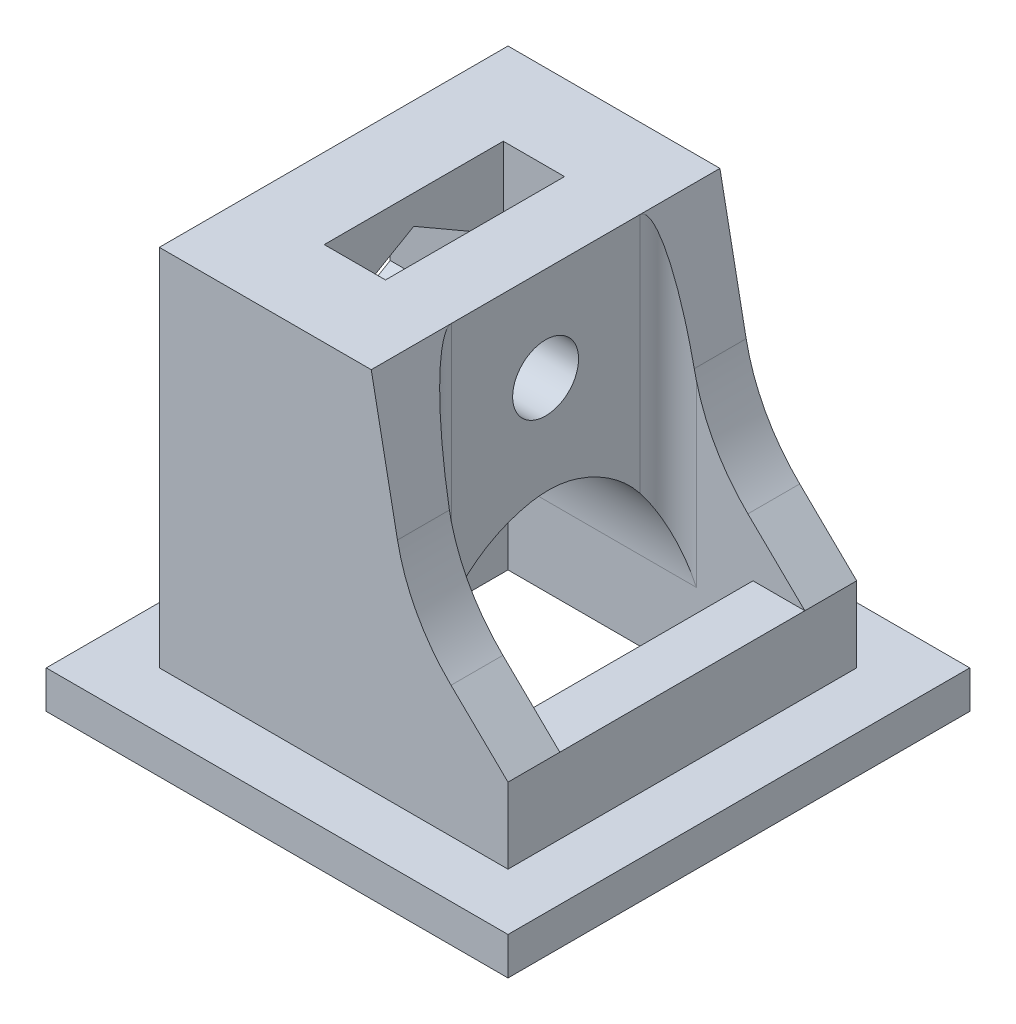
SolidWorks part; units mm, degrees
material "PBT Общее назначение"
ref_plane "Спереди" through (0, 0, 0) normal (0, 0, 1) x (1, 0, 0)
ref_plane "Сверху" through (0, 0, 0) normal (0, 1, 0) x (1, 0, 0)
ref_plane "Справа" through (0, 0, 0) normal (1, 0, 0) x (0, 0, -1)
sketch "Эскиз1" plane through (0, 0, 0) normal (0, 1, 0) x (1, 0, 0)
  line L0 (0, 0) -> (18.5, 0)
  line L1 (0, 0) -> (0, 18.5)
  line L2 (18.5, 0) -> (18.5, 18.5)
  line L3 (0, 18.5) -> (18.5, 18.5)
  line L4 (2.75, 15.75) -> (2.75, 2.75)
  line L5 (2.75, 15.75) -> (15.75, 15.75)
  line L6 (2.75, 2.75) -> (15.75, 2.75)
  line L7 (15.75, 15.75) -> (15.75, 2.75)
  line L8 (9.25, 18.5) -> (9.25, 0) construction
  line L9 (18.5, 9.25) -> (0, 9.25) construction
  line L10 (2.75, 9.25) -> (15.75, 9.25) construction
  line L11 (9.25, 15.75) -> (9.25, 2.75) construction
  dimension "D1" = 18.5
  dimension "D3" = 13
extrude "Бобышка-Вытянуть1" add sketch "Эскиз1" along normal blind 4
sketch "Эскиз2" plane through (0, 0, 0) normal (0, 0, 1) x (1, 0, 0)
  line L0 (0, 4) -> (18.5, 4)
  line L1 (18.5, 4) -> (0, 22)
  line L2 (0, 4) -> (0, 22)
  dimension "D1" = 18
extrude "Бобышка-Вытянуть2" add sketch "Эскиз2" against normal up to surface (18.5 mm away) up to face at (9.25, 2, -18.5)
sketch "Эскиз3" plane through (0, 4, 0) normal (0, -1, 0) x (1, 0, 0)
  line L4 (2.75, -2.75) -> (2.75, -15.75)
  line L5 (2.75, -15.75) -> (15.75, -15.75)
  line L6 (15.75, -15.75) -> (15.75, -2.75)
  line L7 (15.75, -2.75) -> (2.75, -2.75)
  line L8 (2.75, -2.75) -> (2.75, -15.75)
  line L9 (2.75, -15.75) -> (15.75, -15.75)
  line L10 (15.75, -15.75) -> (15.75, -2.75)
  line L11 (15.75, -2.75) -> (2.75, -2.75)
  dimension "D1" = 0
extrude "Вырез-Вытянуть1" cut sketch "Эскиз3" against normal through all
sketch "Эскиз4" plane through (15.75, 0, 0) normal (-1, 0, 0) x (0, 0, 1)
  line L0 (0, 4) -> (-18.5, 4) construction
  line L1 (-2.75, 4) -> (-15.75, 4)
  line L2 (-2.75, 6.6757) -> (-2.75, 0) construction
  line L3 (-2.75, 6.6757) -> (-2.75, 4)
  line L4 (-15.75, 6.6757) -> (-15.75, 0) construction
  line L5 (-15.75, 6.6757) -> (-15.75, 4)
  line L6 (-2.75, 6.6757) -> (-15.75, 6.6757) construction
  line L7 (-2.75, 6.6757) -> (-15.75, 6.6757)
extrude "Вырез-Вытянуть2" cut sketch "Эскиз4" against normal through all
sketch "Эскиз6" plane through (0, 0, -18.5) normal (0, 0, -1) x (-1, 0, 0)
  line L1 (-2.75, 19.3243) -> (-2.75, 0) construction
  line L2 (-2.75, 19.3243) -> (0, 19.3243)
  line L3 (0, 22) -> (0, 0) construction
  line L4 (0, 22) -> (0, 19.3243)
  line L5 (0, 22) -> (-18.5, 4) construction
  line L6 (0, 22) -> (-2.75, 19.3243)
  line L7 (-2.75, 19.3243) -> (-2.75, 0) construction
extrude "Вырез-Вытянуть3" cut sketch "Эскиз6" against normal through all
sketch "Эскиз7" plane through (0, 0, 0) normal (0, -1, 0) x (1, 0, 0)
  line L0 (0, -9.25) -> (18.5, -9.25) construction
  line L1 (0, -18.5) -> (0, 0) construction
  line L2 (18.5, 0) -> (18.5, -18.5) construction
  line L3 (9.25, -18.5) -> (9.25, 0) construction
  line L4 (18.5, -18.5) -> (0, -18.5) construction
  line L5 (0, 0) -> (18.5, 0) construction
sketch "Эскиз9" plane through (0, 0, 0) normal (0, -1, 0) x (1, 0, 0)
  line L0 (15.75, -2.75) -> (15.75, -15.75) construction
  line L1 (15.75, -15.75) -> (2.75, -15.75) construction
  line L2 (2.75, -15.75) -> (2.75, -2.75) construction
  line L3 (2.75, -2.75) -> (15.75, -2.75) construction
  line L4 (0, 0) -> (0, -18.5)
  line L5 (0, -18.5) -> (18.5, -18.5)
  line L6 (18.5, -18.5) -> (18.5, 0)
  line L7 (18.5, 0) -> (0, 0)
  line L8 (0, 0) -> (0, -18.5)
  line L9 (0, -18.5) -> (18.5, -18.5)
  line L10 (18.5, -18.5) -> (18.5, 0)
  line L11 (18.5, 0) -> (0, 0)
  line L12 (15.75, -2.75) -> (15.75, -15.75)
  line L13 (15.75, -15.75) -> (2.75, -15.75)
  line L14 (2.75, -15.75) -> (2.75, -2.75)
  line L15 (2.75, -2.75) -> (15.75, -2.75)
  dimension "D1" = 0
extrude "Бобышка-Вытянуть4" add sketch "Эскиз9" along normal blind 2
sketch "Эскиз10" plane through (0, -2, 0) normal (0, -1, 0) x (1, 0, 0)
  line L0 (21.5, -21.5) -> (-3, -21.5)
  line L1 (21.5, -21.5) -> (21.5, 3)
  line L2 (-3, -21.5) -> (-3, 3)
  line L3 (21.5, 3) -> (-3, 3)
  line L4 (2.75, -15.75) -> (15.75, -15.75) construction
  line L5 (15.75, -15.75) -> (15.75, -2.75) construction
  line L6 (2.75, -2.75) -> (2.75, -15.75) construction
  line L7 (15.75, -2.75) -> (2.75, -2.75) construction
  line L8 (2.75, -15.75) -> (15.75, -15.75)
  line L9 (15.75, -15.75) -> (15.75, -2.75)
  line L10 (2.75, -2.75) -> (2.75, -15.75)
  line L11 (15.75, -2.75) -> (2.75, -2.75)
  line L12 (9.25, -21.5) -> (9.25, 3) construction
  line L13 (-3, -9.25) -> (21.5, -9.25) construction
  line L14 (18.5, -18.5) -> (18.5, 0) construction
  line L15 (0, -18.5) -> (18.5, -18.5) construction
  point P12 (18.5, -9.25)
  point P13 (9.25, -18.5)
  dimension "D1" = 24.5
extrude "Бобышка-Вытянуть5" add sketch "Эскиз10" against normal blind 2
sketch "Эскиз12" plane through (0, 0, -15.75) normal (0, 0, 1) x (1, 0, 0)
  line L0 (2.75, 19.3243) -> (2.75, -2) construction
  line L1 (18.5, 4) -> (2.75, 19.3243) construction
  line L2 (2.75, 19.3243) -> (2.75, 6)
  line L3 (4.25, 17.8649) -> (2.75, 19.3243)
  line L4 (2.75, -2) -> (15.75, -2) construction
  line L5 (4.25, 9.1225) -> (4.25, 17.8649)
  arc A0 (4.25, 9.1225) -> (2.75, 6) centre (6.75, 6) ccw
  dimension "D2" = 4
  dimension "D1" = 1.5
  dimension "D3" = 8
extrude "Бобышка-Вытянуть6" add sketch "Эскиз12" along normal up to surface (13 mm away) up to face at (11.1, 4.6649, -2.75)
sketch "Эскиз13" plane through (0, 0, 0) normal (-1, 0, 0) x (0, 0, 1)
  line L0 (-9.25, 19.3243) -> (-9.25, 8.0835) construction
  line L1 (0, 19.3243) -> (-18.5, 19.3243) construction
  circle A0 centre (-9.25, 14.3243) radius 1.75
  dimension "D1" = 3.5
  dimension "D2" = 5
extrude "Вырез-Вытянуть4" cut sketch "Эскиз13" against normal through all
sketch "Эскиз15" plane through (0, 0, -15.75) normal (0, 0, 1) x (1, 0, 0)
  line L0 (4.25, 9.1225) -> (4.25, 17.8649) construction
  line L1 (4.25, 9.1225) -> (4.25, 17.8649)
  line L2 (18.5, 4) -> (4.25, 17.8649) construction
  line L3 (7.25, 14.9459) -> (4.25, 17.8649)
  line L4 (4.25, 9.1225) -> (7.25, 11.9459)
  line L5 (7.25, 11.9459) -> (7.25, 14.9459)
  dimension "D2" = 3
  dimension "D1" = 3
extrude "Бобышка-Вытянуть7" add sketch "Эскиз15" along normal blind 1.75
ref_plane "Плоскость1" through (0, 0, -9.25) normal (0, 0, -1) x (1, 0, 0)
mirror "Зеркальное отражение1" about plane through (0, 0, -9.25) normal (0, 0, -1) of "Бобышка-Вытянуть7"
sketch "Эскиз16" plane through (0, 0, 0) normal (0, 0, 1) x (1, 0, 0)
  line L1 (7.25, 11.9459) -> (7.25, 14.9459) construction
  line L2 (18.5, 4) -> (2.75, 19.3243) construction
  line L3 (7.25, 14.9459) -> (2.75, 19.3243)
  line L4 (7.25, 14.9459) -> (7.25, 19.3243)
  line L6 (2.75, 19.3243) -> (7.25, 19.3243)
extrude "Бобышка-Вытянуть8" add sketch "Эскиз16" against normal up to surface (18.5 mm away) up to face at (7.95, 8.5297, -18.5)
sketch "Эскиз17" plane through (0, 19.3243, 0) normal (0, 1, 0) x (1, 0, 0)
  line L4 (7.25, 14) -> (4.25, 14)
  line L5 (7.25, 4.5) -> (7.25, 14)
  line L6 (4.25, 4.5) -> (7.25, 4.5)
  line L7 (4.25, 14) -> (4.25, 4.5)
  line L8 (7.25, 14) -> (4.25, 14)
  line L9 (7.25, 4.5) -> (7.25, 14)
  line L10 (4.25, 4.5) -> (7.25, 4.5)
  line L11 (4.25, 14) -> (4.25, 4.5)
  dimension "D1" = 0
extrude "Вырез-Вытянуть6" cut sketch "Эскиз17" against normal through all
fillet "Скругление1" radius 15 1 edges at (7.25, 14.9459, -1.375)
fillet "Скругление2" radius 15 1 edges at (7.25, 14.9459, -17.125)
sketch "Эскиз18" plane through (7.25, 0, 0) normal (1, 0, 0) x (0, 0, -1)
  line L4 (4.5, 19.3243) -> (2.75, 19.3243)
  line L5 (2.75, 19.3243) -> (2.75, 11.9459)
  line L6 (2.75, 11.9459) -> (4.5, 11.9459)
  line L7 (4.5, 11.9459) -> (4.5, 19.3243)
  line L8 (4.5, 19.3243) -> (2.75, 19.3243)
  line L9 (2.75, 19.3243) -> (2.75, 11.9459)
  line L10 (2.75, 11.9459) -> (4.5, 11.9459)
  line L11 (4.5, 11.9459) -> (4.5, 19.3243)
  line L12 (15.75, 11.9459) -> (15.75, 19.3243)
  line L13 (15.75, 19.3243) -> (14, 19.3243)
  line L14 (14, 19.3243) -> (14, 11.9459)
  line L15 (14, 11.9459) -> (15.75, 11.9459)
  line L16 (15.75, 11.9459) -> (15.75, 19.3243)
  line L17 (15.75, 19.3243) -> (14, 19.3243)
  line L18 (14, 19.3243) -> (14, 11.9459)
  line L19 (14, 11.9459) -> (15.75, 11.9459)
  dimension "D1" = 0
  dimension "D2" = 0
extrude "Бобышка-Вытянуть9" add sketch "Эскиз18" along normal up to surface (3.2258 mm away) up to face at (9.0866, 14.816, -1.375)
sketch "Эскиз19" plane through (0, 0, 0) normal (-1, 0, 0) x (0, 0, 1)
  circle A0 centre (-9.25, 14.3243) radius 1.75 construction
  circle A1 centre (-9.25, 14.3243) radius 1.75 construction
  circle A2 centre (-9.25, 14.3243) radius 5
  dimension "D1" = 10
sketch "Эскиз14" plane through (0, 0, 0) normal (-1, 0, 0) x (0, 0, 1)
  line L0 (-9.25, 14.3243) -> (-9.25, 17.7884) construction
  line L1 (-9.25, 10.8602) -> (-6.25, 12.5923)
  line L2 (-6.25, 12.5923) -> (-6.25, 16.0564)
  line L3 (-6.25, 16.0564) -> (-9.25, 17.7884)
  line L4 (-9.25, 17.7884) -> (-12.25, 16.0564)
  line L5 (-12.25, 16.0564) -> (-12.25, 12.5923)
  line L6 (-12.25, 12.5923) -> (-9.25, 10.8602)
  circle A0 centre (-9.25, 14.3243) radius 3 construction
  dimension "D1" = 6
extrude "Вырез-Вытянуть5" cut sketch "Эскиз14" along normal through all and the other way up to surface (4.25 mm away) other way up to face at (4.25, 14.3243, -7.5)
sketch "Эскиз21" plane through (0, 0, -4.5) normal (0, 0, -1) x (-1, 0, 0)
  line L0 (-4.25, 9.1225) -> (-7.25, 11.9459) construction
  line L1 (-10.4758, 11.9459) -> (-7.25, 11.9459) construction
  line L2 (-4.25, 9.1225) -> (-7.25, 11.9459)
  line L3 (-10.4758, 11.9459) -> (-7.25, 11.9459)
  line L4 (-4.25, 9.1225) -> (-13.5183, 9.1225)
  arc A0 (-11.6421, 10.6726) -> (-10.4758, 11.9459) centre (-22.1024, 21.4235) ccw construction
  arc A1 (-13.5183, 9.1225) -> (-10.4758, 11.9459) centre (-22.1024, 21.4235) ccw
extrude "Бобышка-Вытянуть11" add sketch "Эскиз21" against normal up to surface (1.75 mm away) up to face at (9.8604, 5.9823, -2.75)
sketch "Эскиз22" plane through (0, 0, -14) normal (0, 0, 1) x (1, 0, 0)
  line L0 (10.4758, 11.9459) -> (7.25, 11.9459) construction
  line L1 (4.25, 9.1225) -> (7.25, 11.9459) construction
  line L2 (10.4758, 11.9459) -> (7.25, 11.9459)
  line L3 (4.25, 9.1225) -> (7.25, 11.9459)
  line L4 (4.25, 9.1225) -> (13.5183, 9.1225)
  arc A0 (10.4758, 11.9459) -> (11.6421, 10.6726) centre (22.1024, 21.4235) ccw construction
  arc A1 (10.4758, 11.9459) -> (13.5183, 9.1225) centre (22.1024, 21.4235) ccw
extrude "Бобышка-Вытянуть12" add sketch "Эскиз22" against normal up to surface (1.75 mm away) up to face at (9.8604, 5.9823, -15.75)
sketch "Эскиз23" plane through (0, 0, -15.75) normal (0, 0, -1) x (-1, 0, 0)
  line L2 (-13.2352, 9.1225) -> (-11.6421, 10.6726)
  line L3 (-13.5183, 9.1225) -> (-13.2352, 9.1225)
  line L4 (-13.2352, 9.1225) -> (-11.6421, 10.6726)
  line L5 (-13.5183, 9.1225) -> (-13.2352, 9.1225)
  arc A1 (-13.5183, 9.1225) -> (-11.6421, 10.6726) centre (-22.1024, 21.4235) ccw
  arc A2 (-13.5183, 9.1225) -> (-11.6421, 10.6726) centre (-22.1024, 21.4235) ccw
  dimension "D1" = 0
extrude "Вырез-Вытянуть7" cut sketch "Эскиз23" against normal through all
sketch "Эскиз20" plane through (0, 19.3243, 0) normal (0, 1, 0) x (1, 0, 0)
  line L0 (7.25, 0) -> (7.25, 18.5)
  line L1 (7.25, 0) -> (13.2352, 0)
  line L2 (7.25, 18.5) -> (13.2352, 18.5)
  line L5 (13.2352, 2.75) -> (13.2352, 4.5) construction
  line L6 (13.2352, 0) -> (13.2352, 18.5)
extrude "Бобышка-Вытянуть15" add sketch "Эскиз20" against normal up to surface (4.3784 mm away) up to face at (14.4591, 7.9317, -2.4167)
sketch "Эскиз25" plane through (0, 0, -4.5) normal (0, 0, -1) x (-1, 0, 0)
  line L0 (-13.2352, 9.1225) -> (-4.25, 9.1225) construction
  line L1 (-13.2352, 9.1225) -> (-7.25, 9.1225)
  line L2 (-7.25, 14.9459) -> (-13.2352, 9.1225) construction
  line L3 (-7.25, 14.9459) -> (-13.2352, 9.1225)
  line L4 (-7.25, 14.9459) -> (-7.25, 9.1225)
extrude "Бобышка-Вытянуть16" add sketch "Эскиз25" along normal up to surface (9.5 mm away) up to face at (7.247, 14.3679, -14)
sketch "Эскиз27" plane through (7.25, 0, 0) normal (-1, 0, 0) x (0, 0, 1)
  line L0 (-9.25, 17.7884) -> (-9.25, 10.8602) construction
  line L6 (-9.25, 10.8602) -> (-6.25, 12.5923)
  line L7 (-6.25, 12.5923) -> (-6.25, 16.0564)
  line L8 (-6.25, 16.0564) -> (-9.25, 17.7884)
  line L9 (-9.25, 17.7884) -> (-12.25, 16.0564)
  line L10 (-12.25, 16.0564) -> (-12.25, 12.5923)
  line L11 (-12.25, 12.5923) -> (-9.25, 10.8602)
  line L12 (-9.25, 10.8602) -> (-6.25, 12.5923) construction
  line L13 (-6.25, 12.5923) -> (-6.25, 16.0564) construction
  line L14 (-6.25, 16.0564) -> (-9.25, 17.7884) construction
  line L15 (-9.25, 17.7884) -> (-12.25, 16.0564) construction
  line L16 (-12.25, 16.0564) -> (-12.25, 12.5923) construction
  line L17 (-12.25, 12.5923) -> (-9.25, 10.8602) construction
  circle A1 centre (-9.25, 14.3243) radius 1.75
  dimension "D2" = 3.5
  dimension "D1" = 0
extrude "Вырез-Вытянуть10" cut sketch "Эскиз27" against normal through all
sketch "Эскиз28" plane through (13.2352, 0, 0) normal (1, 0, 0) x (0, 0, -1)
  line L0 (2.75, 9.1225) -> (2.75, 4) construction
  line L1 (2.75, 19.3243) -> (2.75, 9.1225)
  line L2 (15.75, 4) -> (15.75, 9.1225) construction
  line L3 (15.75, 9.1225) -> (15.75, 19.3243)
  line L4 (0, 19.3243) -> (18.5, 19.3243) construction
  line L5 (2.75, 9.1225) -> (15.75, 9.1225) construction
  line L6 (2.75, 9.1225) -> (15.75, 9.1225)
  line L7 (2.75, 19.3243) -> (15.75, 19.3243)
extrude "Вырез-Вытянуть11" cut sketch "Эскиз28" against normal blind 1.99
sketch "Эскиз29" plane through (0, 0, -18.5) normal (0, 0, -1) x (-1, 0, 0)
  line L1 (-13.2352, 9.1225) -> (-13.2352, 19.3243) construction
  line L5 (-11.2452, 19.3243) -> (-13.2352, 9.1225)
  line L7 (-13.2352, 9.1225) -> (-13.2352, 19.3243)
  line L8 (-11.2452, 19.3243) -> (-13.2352, 19.3243) construction
  line L9 (-11.2452, 19.3243) -> (-13.2352, 19.3243)
extrude "Вырез-Вытянуть12" cut sketch "Эскиз29" against normal through all
fillet "Скругление9" radius 10 2 edges at (13.2352, 9.1225, -1.375) (13.2352, 9.1225, -17.125)
fillet "Скругление10" radius 7 1 edges at (7.7476, 9.1225, -2.75)
fillet "Скругление11" radius 7 1 edges at (7.7476, 9.1225, -15.75)
fillet "Скругление12" radius 5 1 edges at (9.2476, 9.1225, -9.75)
fillet "Скругление13" radius 1.5 1 edges at (11.2452, 10.7593, -15.75)
fillet "Скругление14" radius 1.5 1 edges at (11.2452, 10.7234, -2.75)
sketch "Эскиз30" plane through (7.25, 0, 0) normal (-1, 0, 0) x (0, 0, 1)
  line L3 (-14, 19.3243) -> (-14, 6.8244)
  line L4 (-4.5, 6.7526) -> (-4.5, 19.3243)
  line L5 (-4.5, 19.3243) -> (-14, 19.3243)
  line L6 (-14, 19.3243) -> (-14, 6.8244)
  line L7 (-4.5, 6.7526) -> (-4.5, 19.3243)
  line L8 (-4.5, 19.3243) -> (-14, 19.3243)
  arc A3 (-10.9853, 8.8278) -> (-14, 6.8244) centre (-8.75, 2.1943) ccw
  arc A4 (-8.4853, 9.0073) -> (-10.9853, 8.8278) centre (-9.3887, 4.0896) ccw
  arc A5 (-4.5, 6.7526) -> (-8.4853, 9.0073) centre (-9.75, 2.1225) ccw
  arc A6 (-10.9853, 8.8278) -> (-14, 6.8244) centre (-8.75, 2.1943) ccw
  arc A7 (-8.4853, 9.0073) -> (-10.9853, 8.8278) centre (-9.3887, 4.0896) ccw
  arc A8 (-4.5, 6.7526) -> (-8.4853, 9.0073) centre (-9.75, 2.1225) ccw
  dimension "D1" = 0
extrude "Вырез-Вытянуть13" cut sketch "Эскиз30" against normal blind 0.25
